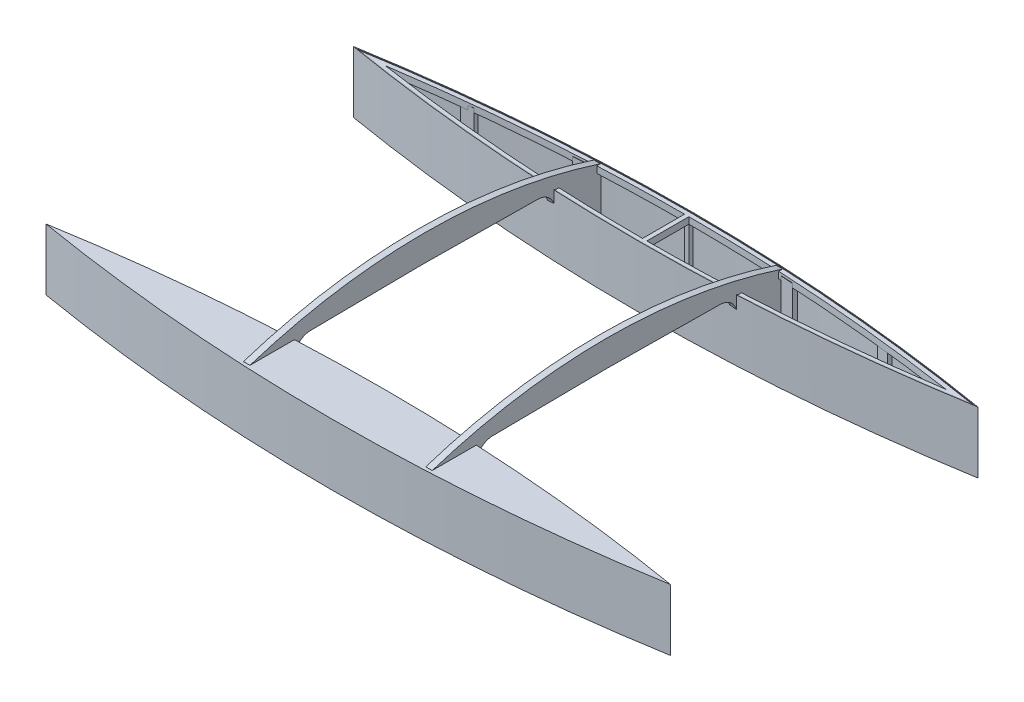
SolidWorks part; units mm, degrees
ref_plane "Front Plane"
ref_plane "Top Plane" through (0, 0, 0) normal (0, 1, 0) x (1, 0, 0)
ref_plane "Right Plane" through (0, 0, 0) normal (1, 0, 0) x (0, 0, -1)
sketch "Sketch1" plane through (0, 0, 0) normal (0, 1, 0) x (1, 0, 0)
  arc A4 (-914.4, 0) -> (914.4, 0) centre (0, -5448.3) cw
  arc A5 (-914.4, 0) -> (914.4, 0) centre (0, 5448.2999) ccw
  point P8 (0, 76.2)
extrude "Boss-Extrude1" add sketch "Sketch1" along normal blind 180
shell "Shell4" thickness 2 removed face at (0, 180, 0)
sketch "Sketch4" plane through (0, 2, 0) normal (0, 1, 0) x (1, 0, 0)
  line L0 (0, -83.82) -> (0, 83.82) construction
  line L1 (6.35, 61.4963) -> (6.35, -61.4963)
  line L2 (-6.35, 61.4963) -> (-6.35, -61.4963)
  line L5 (6.35, 61.4963) -> (6.35, -61.4963)
  arc A0 (902.238, 0) -> (-902.238, 0) centre (0, 5448.2999) cw
  arc A1 (-902.238, 0) -> (902.238, 0) centre (0, 5448.2999) ccw construction
  arc A2 (-902.238, 0) -> (902.238, 0) centre (0, 5448.2999) ccw construction
  arc A3 (902.238, 0) -> (-902.238, 0) centre (0, -5448.3) ccw
  arc A4 (-6.35, 61.4963) -> (-820.9282, 0) centre (0, -5448.3) ccw
  arc A5 (-6.35, -61.4963) -> (-820.9282, 0) centre (0, 5448.2999) cw
  arc A6 (820.9282, 0) -> (-820.9282, 0) centre (0, -5448.3) ccw construction
  arc A7 (820.9282, 0) -> (-820.9282, 0) centre (0, 5448.2999) cw construction
  arc A8 (6.35, 61.4963) -> (820.9282, 0) centre (0, -5448.3) cw
  arc A9 (6.35, -61.4963) -> (820.9282, 0) centre (0, 5448.2999) ccw
  arc M5 (-902.238, 0) -> (902.238, 0) centre (0, 5448.2999) ccw
  arc M6 (902.238, 0) -> (-902.238, 0) centre (0, -5448.3) ccw
  dimension "D1" = 12.7
extrude "Boss-Extrude2" add sketch "Sketch4" along normal blind 19.05 contours A9 L1 A8 L2 A5 A4 M6 M5 region at (0, 2, 0)
sketch "Sketch5" plane through (0, 21.05, 0) normal (0, 1, 0) x (1, 0, 0)
  line L0 (-902.238, 0) -> (-858.3563, 7.0855)
  line L1 (-858.3563, 7.0855) -> (-858.3563, -7.0855)
  line L2 (-902.238, 0) -> (-858.3563, -7.0855)
  line L3 (0, -83.82) -> (0, 83.82) construction
  line L4 (902.238, 0) -> (858.3563, -7.0855)
  line L5 (858.3563, 7.0855) -> (858.3563, -7.0855)
  line L6 (902.238, 0) -> (858.3563, 7.0855)
  line L7 (-99, 0) -> (99, 0) construction
  line L8 (591.7736, -42.4022) -> (609.6, -39.5463)
  line L15 (590.3747, -29.7794) -> (591.7736, -42.4022)
  line L16 (623.4423, -26.1146) -> (590.3747, -29.7794)
  line L17 (624.7366, -37.4797) -> (623.4423, -26.1146)
  line L18 (-609.6, 39.5463) -> (-591.8311, 41.5626)
  line L19 (-591.8311, 41.5626) -> (-590.4149, 29.0822)
  line L20 (-590.4149, 29.0822) -> (-626.732, 25.739)
  line L21 (-626.732, 25.739) -> (-627.8128, 37.4797)
  line L22 (-627.8128, 37.4797) -> (-609.6, 39.5463)
  line L23 (-304.8, 65.7823) -> (-282.7554, 66.9566)
  line L24 (-282.7554, 66.9566) -> (-282.0245, 53.2371)
  line L25 (-282.0245, 53.2371) -> (-323.9429, 51.004)
  line L26 (-323.9429, 51.004) -> (-324.7463, 64.6435)
  line L27 (-324.7463, 64.6435) -> (-304.8, 65.7823)
  line L28 (-6.35, 61.4963) -> (-6.35, 74.1963)
  line L29 (-6.35, 74.1963) -> (6.35, 74.1963)
  line L30 (6.35, 74.1963) -> (6.35, 61.4963)
  line L31 (6.35, 61.4963) -> (-6.35, 61.4963)
  line L32 (304.8, 65.7823) -> (320.7613, 64.8768)
  line L33 (320.7613, 64.8768) -> (319.9743, 51.004)
  line L34 (319.9743, 51.004) -> (284.5401, 53.0141)
  line L35 (284.5401, 53.0141) -> (285.2546, 66.8279)
  line L36 (285.2546, 66.8279) -> (304.8, 65.7823)
  line L37 (609.6, 39.5463) -> (624.7366, 37.4797)
  line L38 (624.7366, 37.4797) -> (623.4423, 26.1146)
  line L39 (623.4423, 26.1146) -> (590.3747, 29.7794)
  line L40 (590.3747, 29.7794) -> (591.7736, 42.4022)
  line L41 (591.7736, 42.4022) -> (609.6, 39.5463)
  line L42 (609.6, -39.5463) -> (624.7366, -37.4797)
  line L43 (285.2546, -66.8279) -> (304.8, -65.7823)
  line L44 (284.5401, -53.0141) -> (285.2546, -66.8279)
  line L45 (319.9743, -51.004) -> (284.5401, -53.0141)
  line L46 (320.7613, -64.8768) -> (319.9743, -51.004)
  line L47 (304.8, -65.7823) -> (320.7613, -64.8768)
  line L48 (6.35, -61.4963) -> (-6.35, -61.4963)
  line L49 (6.35, -74.1963) -> (6.35, -61.4963)
  line L50 (-6.35, -74.1963) -> (6.35, -74.1963)
  line L51 (-6.35, -61.4963) -> (-6.35, -74.1963)
  line L52 (-324.7463, -64.6435) -> (-304.8, -65.7823)
  line L53 (-323.9429, -51.004) -> (-324.7463, -64.6435)
  line L54 (-282.0245, -53.2371) -> (-323.9429, -51.004)
  line L55 (-282.7554, -66.9566) -> (-282.0245, -53.2371)
  line L56 (-304.8, -65.7823) -> (-282.7554, -66.9566)
  line L57 (-627.8128, -37.4797) -> (-609.6, -39.5463)
  line L58 (-626.732, -25.739) -> (-627.8128, -37.4797)
  line L59 (-590.4149, -29.0822) -> (-626.732, -25.739)
  line L60 (-591.8311, -41.5626) -> (-590.4149, -29.0822)
  line L61 (-609.6, -39.5463) -> (-591.8311, -41.5626)
  arc A0 (902.238, 0) -> (-902.238, 0) centre (0, -5448.3) ccw construction
  arc A1 (-902.238, 0) -> (902.238, 0) centre (0, 5448.2999) ccw construction
  arc A2 (-6.35, 61.4963) -> (-820.9282, 0) centre (0, -5448.3) ccw construction
  arc A3 (902.238, 0) -> (-902.238, 0) centre (0, -5448.3) ccw construction
  arc A4 (820.9282, 0) -> (6.35, 61.4963) centre (0, -5448.3) ccw construction
  arc A5 (820.9282, 0) -> (6.35, 61.4963) centre (0, -5448.3) ccw construction
extrude "Boss-Extrude7" add sketch "Sketch5" along normal blind 150 separate body
ref_plane "Plane1" through (0, 90, 0) normal (0, 1, 0) x (1, 0, 0)
mirror "Mirror1" about plane through (0, 90, 0) normal (0, 1, 0) of "Boss-Extrude2"
ref_plane "Plane2" through (-276.35, 0, 0) normal (-1, 0, 0) x (0, 0, 1)
ref_plane "Plane3" through (283.65, 0, 0) normal (-1, 0, 0) x (0, 0, 1)
sketch "Sketch9" plane through (-276.35, 0, 0) normal (-1, 0, 0) x (0, 0, 1)
  line L2 (450.0431, 183.3031) -> (117.4545, 179.6422)
  line L3 (450.0431, 183.3031) -> (450.0431, 260.3601)
  line L4 (-67.3347, 177.6082) -> (-67.3347, 0)
  line L5 (-76.2, 0) -> (0, 0) construction
  line L6 (67.2136, 128.8453) -> (67.2136, 0)
  line L7 (832.8725, 128.8453) -> (832.8725, 0)
  line L8 (967.4208, 177.6082) -> (967.4208, 0)
  line L9 (450.0431, 183.3031) -> (782.6317, 179.6422)
  line L10 (-67.3347, 0) -> (67.2136, 0)
  line L11 (967.4208, 0) -> (832.8725, 0)
  arc A0 (-67.3347, 177.6082) -> (967.4208, 177.6082) centre (450.0431, -1398.3772) cw
  arc A1 (117.4545, 179.6422) -> (67.2136, 128.8453) centre (118.0136, 128.8453) ccw
  arc A2 (782.6317, 179.6422) -> (832.8725, 128.8453) centre (782.0725, 128.8453) cw
extrude "Boss-Extrude8" add sketch "Sketch9" against normal blind 19.05 contours L9 A2 L7 L11 L8 A0 L3 | A1 L2 L3 A0 L4 L10 L6 region at (-276.35, 187.2643, 283.685) region at (-276.35, 221.8316, 455.835)
mirror "Mirror2" about plane through (0, 0, 0) normal (1, 0, 0) of "Boss-Extrude8"
ref_axis "Axis1" through (-257.3, 183.3031, 450.0431) along (1, 0, 0)
ref_plane "Plane4" through (0, 0, 450.0431) normal (0, 0, 1) x (1, 0, 0)
mirror "Mirror7" about plane through (0, 0, 450.0431) normal (0, 0, 1) of "Boss-Extrude1"
